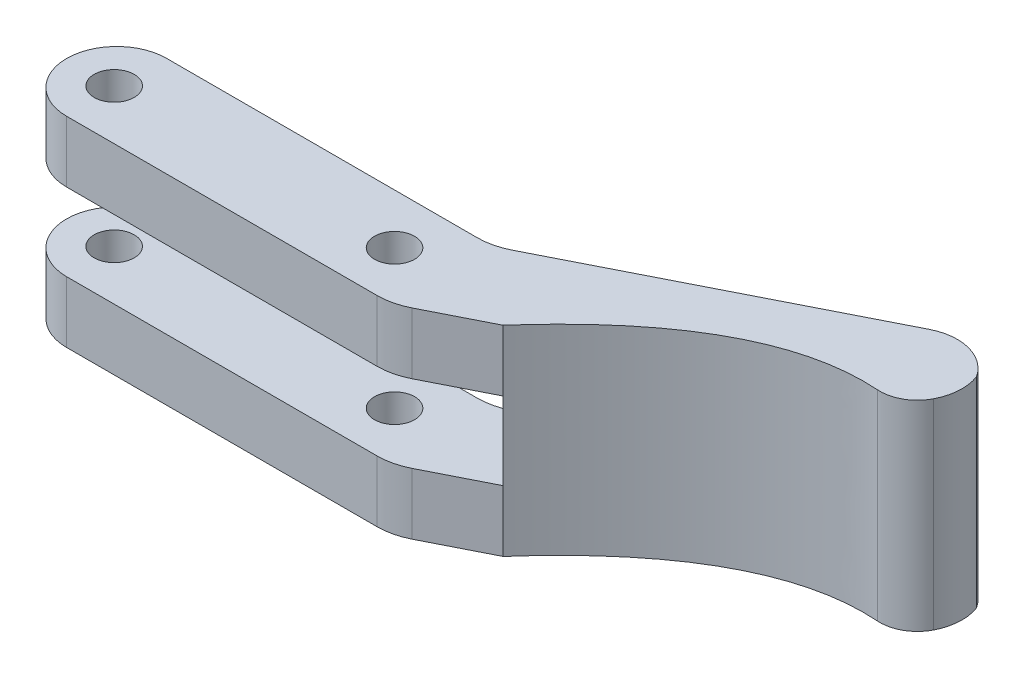
SolidWorks part; units mm, degrees
ref_plane "前视基准面" through (0, 0, 0) normal (0, 0, 1) x (1, 0, 0)
ref_plane "上视基准面" through (0, 0, 0) normal (0, 1, 0) x (1, 0, 0)
ref_plane "右视基准面" through (0, 0, 0) normal (1, 0, 0) x (0, 0, -1)
sketch "草图1" plane through (0, 0, 0) normal (0, 1, 0) x (1, 0, 0)
  line L0 (0, -55) -> (0, 55) construction
  line L1 (-15, 4) -> (15, 4)
  line L2 (-15, 4) -> (-15, -4)
  line L3 (-15, -4) -> (15, -4)
  line L4 (15, 4) -> (15, -4)
  line L5 (-15, 4) -> (15, -4) construction
  line L6 (-15, -4) -> (15, 4) construction
  circle A0 centre (-11.2, 0) radius 1.6
  circle A1 centre (11.2, 0) radius 1.6
  point P0 (0, 0)
  dimension "D2" = 3.2
  dimension "D1" = 11.2
  dimension "D3" = 8
  dimension "D4" = 30
extrude "凸台-拉伸1" add sketch "草图1" along normal blind 5
sketch "草图2" plane through (0, 5, 0) normal (0, 1, 0) x (1, 0, 0)
  line L0 (15, 4) -> (41.7799, 17.5217)
  line L1 (41.7799, 17.5217) -> (44.9987, 11.1469)
  line L2 (44.9987, 11.1469) -> (15, -4)
  line L3 (15, 4) -> (-15, 4) construction
  line L4 (15, 4) -> (15, -4)
  dimension "D1" = 153.21
  dimension "D2" = 30
extrude "凸台-拉伸2" add sketch "草图2" against normal up to surface (5 mm away) up to face at (0, 0, 0)
sketch "草图3" plane through (0, 0, 0) normal (0, -1, 0) x (1, 0, 0)
  line L6 (-15, -4) -> (15, -4)
  line L7 (15, -4) -> (41.7799, -17.5217)
  line L8 (41.7799, -17.5217) -> (44.9987, -11.1469)
  line L9 (44.9987, -11.1469) -> (15, 4)
  line L10 (15, 4) -> (-15, 4)
  line L11 (-15, 4) -> (-15, -4)
  line L12 (-15, -4) -> (15, -4)
  line L13 (15, -4) -> (41.7799, -17.5217)
  line L14 (41.7799, -17.5217) -> (44.9987, -11.1469)
  line L15 (44.9987, -11.1469) -> (15, 4)
  line L16 (15, 4) -> (-15, 4)
  line L17 (-15, 4) -> (-15, -4)
  circle A0 centre (-11.2, 0) radius 1.6 construction
  circle A1 centre (-11.2, 0) radius 1.6
  circle A2 centre (11.2, 0) radius 1.6 construction
  circle A3 centre (11.2, 0) radius 1.6
  dimension "D1" = 0
extrude "凸台-拉伸3" add sketch "草图3" along normal blind 11
sketch "草图4" plane through (0, 0, 0) normal (0, 1, 0) x (1, 0, 0)
  line L0 (17.678, 5.3522) -> (20.8992, -1.0276)
  line L2 (44.9987, 11.1469) -> (41.7799, 17.5217) construction
  line L3 (19.9193, -1.5162) -> (20.8992, -1.0276)
  line L6 (-15, -4) -> (15, -4)
  line L7 (15, -4) -> (44.9987, 11.1469)
  line L8 (44.9987, 11.1469) -> (41.7799, 17.5217)
  line L9 (41.7799, 17.5217) -> (15, 4)
  line L10 (15, 4) -> (-15, 4)
  line L11 (-15, 4) -> (-15, -4)
  line L12 (-15, -4) -> (15, -4)
  line L13 (15, -4) -> (19.9193, -1.5162)
  line L15 (17.678, 5.3522) -> (15, 4)
  line L16 (15, 4) -> (-15, 4)
  line L17 (-15, 4) -> (-15, -4)
  dimension "D2" = 3
  dimension "D1" = 0
extrude "切除-拉伸1" cut sketch "草图4" against normal blind 6.1 and the other way blind 0.1
fillet "圆角1" radius 4 4 edges at (-15, -8.55, -4) (-15, 2.55, -4) (-15, -8.55, 4) (-15, 2.55, 4)
fillet "圆角2" radius 4 2 edges at (41.7799, -3, -17.5217) (44.9987, -3, -11.1469)
sketch "草图5" plane through (0, 5, 0) normal (0, 1, 0) x (1, 0, 0)
  line L0 (20.8967, -1.0226) -> (41.428, 9.344)
  spline S0 degree 3 poles (20.8967, -1.0226) (25.9802, 4.7285) (33.0955, 10.5511) (41.428, 9.344) knots 0 0 0 0 1 1 1 1
extrude "切除-拉伸2" cut sketch "草图5" against normal blind 16
fillet "圆角3" radius 3 1 edges at (41.428, -3, -9.344)
fillet "圆角4" radius 5 4 edges at (15, -8.55, 4) (15, 2.55, 4) (15, -8.55, -4) (15, 2.55, -4)
